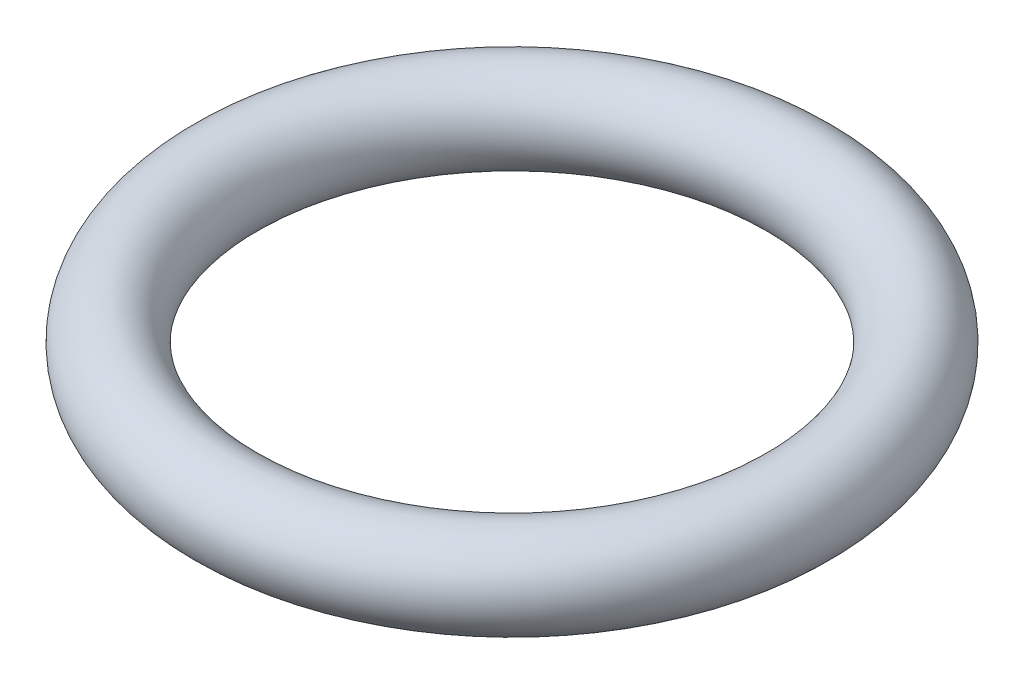
SolidWorks part; units mm, degrees
ref_plane "Front Plane" through (0, 0, 0) normal (0, 0, 1) x (1, 0, 0)
ref_plane "Top Plane" through (0, 0, 0) normal (0, 1, 0) x (1, 0, 0)
ref_plane "Right Plane" through (0, 0, 0) normal (1, 0, 0) x (0, 0, -1)
sketch "Sketch1" plane through (0, 0, 0) normal (1, 0, 0) x (0, 0, -1)
  line L0 (0, 0) -> (0, 24.7958) construction
  line L1 (0, 0) -> (-13, 0) construction
  circle A0 centre (-13, 0) radius 2
  dimension "D1" = 4
  dimension "D2" = 13
revolve "Revolve1" add sketch "Sketch1" angle 360 about L0
ref_axis "Axis1" through (0, -2.2, 0) along (0, 1, 0)
